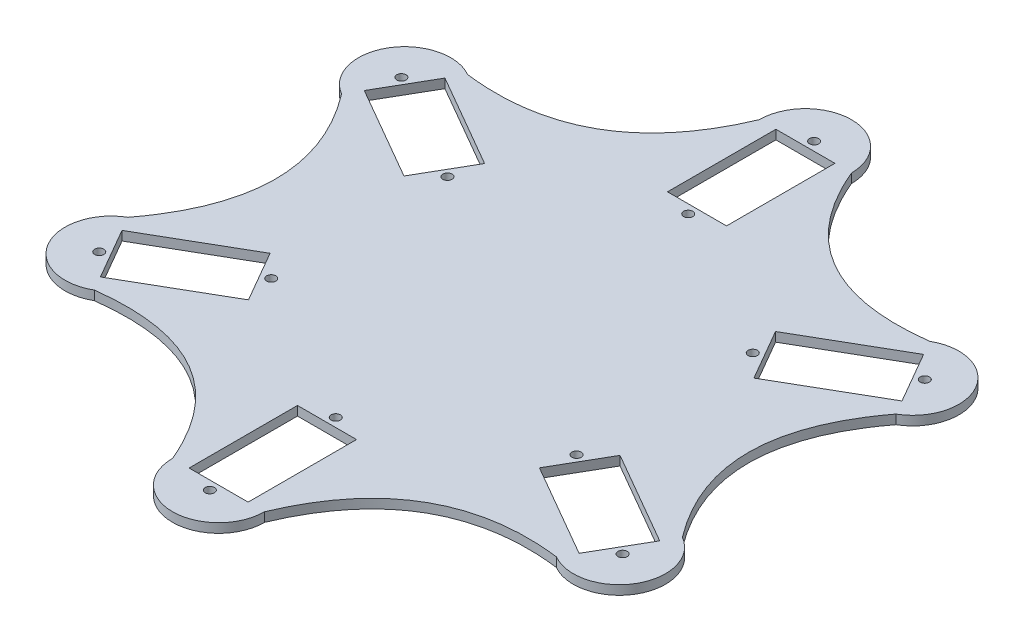
SolidWorks part; units mm, degrees
ref_plane "Front Plane" through (0, 0, 0) normal (0, 0, 1) x (1, 0, 0)
ref_plane "Top Plane" through (0, 0, 0) normal (0, 1, 0) x (1, 0, 0)
ref_plane "Right Plane" through (0, 0, 0) normal (1, 0, 0) x (0, 0, -1)
sketch "Sketch4" plane through (0, 0, 0) normal (0, 1, 0) x (1, 0, 0)
  line L0 (0, 0) -> (0, 73.6122) construction
  line L2 (42.5, 73.6122) -> (-42.5, 73.6122)
  line L5 (-6.4, 40.1122) -> (6.4, 40.1122)
  line L6 (-6.4, 40.1122) -> (-6.4, 63.6122)
  line L7 (-6.4, 63.6122) -> (6.4, 63.6122)
  line L8 (6.4, 40.1122) -> (6.4, 63.6122)
  line L9 (-6.4, 40.1122) -> (6.4, 63.6122) construction
  line L10 (-6.4, 63.6122) -> (6.4, 40.1122) construction
  line L11 (85, 0) -> (42.5, 73.6122)
  line L12 (42.5, 73.6122) -> (0, 0) construction
  line L13 (31.5381, 25.5986) -> (37.9381, 14.5135)
  line L14 (31.5381, 25.5986) -> (51.8897, 37.3486)
  line L15 (51.8897, 37.3486) -> (58.2897, 26.2635)
  line L16 (37.9381, 14.5135) -> (58.2897, 26.2635)
  line L17 (0, 0) -> (63.75, 36.8061) construction
  line L18 (31.5381, 25.5986) -> (58.2897, 26.2635) construction
  line L19 (51.8897, 37.3486) -> (37.9381, 14.5135) construction
  line L21 (42.5, -73.6122) -> (85, 0)
  line L22 (85, 0) -> (0, 0) construction
  line L23 (37.9381, -14.5135) -> (31.5381, -25.5986)
  line L24 (37.9381, -14.5135) -> (58.2897, -26.2635)
  line L25 (58.2897, -26.2635) -> (51.8897, -37.3486)
  line L26 (31.5381, -25.5986) -> (51.8897, -37.3486)
  line L27 (0, 0) -> (63.75, -36.8061) construction
  line L28 (37.9381, -14.5135) -> (51.8897, -37.3486) construction
  line L29 (58.2897, -26.2635) -> (31.5381, -25.5986) construction
  line L30 (0, 0) -> (-42.5, -73.6122) construction
  line L31 (-42.5, -73.6122) -> (42.5, -73.6122)
  line L32 (42.5, -73.6122) -> (0, 0) construction
  line L33 (6.4, -40.1122) -> (-6.4, -40.1122)
  line L34 (6.4, -40.1122) -> (6.4, -63.6122)
  line L35 (6.4, -63.6122) -> (-6.4, -63.6122)
  line L36 (-6.4, -40.1122) -> (-6.4, -63.6122)
  line L37 (0, 0) -> (0, -73.6122) construction
  line L38 (6.4, -40.1122) -> (-6.4, -63.6122) construction
  line L39 (6.4, -63.6122) -> (-6.4, -40.1122) construction
  line L40 (0, 0) -> (-85, 0) construction
  line L41 (-85, 0) -> (-42.5, -73.6122)
  line L43 (-31.5381, -25.5986) -> (-37.9381, -14.5135)
  line L44 (-31.5381, -25.5986) -> (-51.8897, -37.3486)
  line L45 (-51.8897, -37.3486) -> (-58.2897, -26.2635)
  line L46 (-37.9381, -14.5135) -> (-58.2897, -26.2635)
  line L47 (0, 0) -> (-63.75, -36.8061) construction
  line L48 (-31.5381, -25.5986) -> (-58.2897, -26.2635) construction
  line L49 (-51.8897, -37.3486) -> (-37.9381, -14.5135) construction
  line L50 (0, 0) -> (-42.5, 73.6122) construction
  line L51 (-42.5, 73.6122) -> (-85, 0)
  line L53 (-37.9381, 14.5135) -> (-31.5381, 25.5986)
  line L54 (-37.9381, 14.5135) -> (-58.2897, 26.2635)
  line L55 (-58.2897, 26.2635) -> (-51.8897, 37.3486)
  line L56 (-31.5381, 25.5986) -> (-51.8897, 37.3486)
  line L57 (0, 0) -> (-63.75, 36.8061) construction
  line L58 (-37.9381, 14.5135) -> (-51.8897, 37.3486) construction
  line L59 (-58.2897, 26.2635) -> (-31.5381, 25.5986) construction
  line L60 (-6.4, 63.6122) -> (6.4, 63.6122)
  line L61 (-6.4, 63.6122) -> (-6.4, 68.3122) construction
  line L62 (6.4, 63.6122) -> (6.4, 68.3122) construction
  line L63 (-6.4, 68.3122) -> (6.4, 68.3122) construction
  line L64 (-55.0574, 51.8622) -> (55.0574, 51.8622) construction
  line L65 (-10, 63.6122) -> (10, 63.6122) construction
  line L66 (50.0897, 40.4663) -> (60.0897, 23.1458) construction
  line L67 (60.0897, -23.1458) -> (50.0897, -40.4663) construction
  line L68 (10, -63.6122) -> (-10, -63.6122) construction
  line L69 (-50.0897, -40.4663) -> (-60.0897, -23.1458) construction
  line L70 (-60.0897, 23.1458) -> (-50.0897, 40.4663) construction
  line L71 (-10, 63.6122) -> (-21.25, 36.8061) construction
  line L72 (-21.25, 36.8061) -> (-50.0897, 40.4663) construction
  line L73 (50.0897, 40.4663) -> (21.25, 36.8061) construction
  line L74 (21.25, 36.8061) -> (10, 63.6122) construction
  line L75 (60.0897, -23.1458) -> (42.5, 0) construction
  line L76 (42.5, 0) -> (60.0897, 23.1458) construction
  line L77 (10, -63.6122) -> (21.25, -36.8061) construction
  line L78 (21.25, -36.8061) -> (50.0897, -40.4663) construction
  line L79 (-50.0897, -40.4663) -> (-21.25, -36.8061) construction
  line L80 (-21.25, -36.8061) -> (-10, -63.6122) construction
  line L81 (-60.0897, 23.1458) -> (-42.5, 0) construction
  line L82 (-42.5, 0) -> (-60.0897, -23.1458) construction
  circle A0 centre (0, 65.5122) radius 1
  circle A1 centre (56.7352, 32.7561) radius 1
  circle A2 centre (56.7352, -32.7561) radius 1
  circle A3 centre (0, -65.5122) radius 1
  circle A4 centre (-56.7352, -32.7561) radius 1
  circle A5 centre (-56.7352, 32.7561) radius 1
  circle A6 centre (0, 38.2122) radius 1
  circle A7 centre (33.0927, 19.1061) radius 1
  circle A8 centre (33.0927, -19.1061) radius 1
  circle A9 centre (0, -38.2122) radius 1
  circle A10 centre (-33.0927, -19.1061) radius 1
  circle A11 centre (-33.0927, 19.1061) radius 1
  circle A12 centre (0, 0) radius 73.6122
  circle A14 centre (0, 63.6122) radius 10
  circle A15 centre (55.0897, 31.8061) radius 10
  circle A16 centre (55.0897, -31.8061) radius 10
  circle A17 centre (0, -63.6122) radius 10
  circle A18 centre (-55.0897, -31.8061) radius 10
  circle A19 centre (-55.0897, 31.8061) radius 10
  spline S0 degree 2 poles (-10, 63.6122) (-21.25, 36.8061) (-50.0897, 40.4663) knots 0 0 0 1 1 1
  spline S1 degree 2 poles (50.0897, 40.4663) (21.25, 36.8061) (10, 63.6122) knots 0 0 0 1 1 1
  spline S2 degree 2 poles (60.0897, -23.1458) (42.5, 0) (60.0897, 23.1458) knots 0 0 0 1 1 1
  spline S3 degree 2 poles (10, -63.6122) (21.25, -36.8061) (50.0897, -40.4663) knots 0 0 0 1 1 1
  spline S4 degree 2 poles (-50.0897, -40.4663) (-21.25, -36.8061) (-10, -63.6122) knots 0 0 0 1 1 1
  spline S5 degree 2 poles (-60.0897, 23.1458) (-42.5, 0) (-60.0897, -23.1458) knots 0 0 0 1 1 1
  point P0 (0, 73.6122)
  point P6 (0, 51.8622)
  point P14 (63.75, 36.8061)
  point P16 (0, 0)
  point P18 (44.9139, 25.9311)
  point P23 (63.75, -36.8061)
  point P27 (44.9139, -25.9311)
  point P32 (0, -73.6122)
  point P36 (0, -51.8622)
  point P41 (-63.75, -36.8061)
  point P45 (-44.9139, -25.9311)
  point P50 (-63.75, 36.8061)
  point P52 (-56.7352, 32.7561)
  point P54 (-44.9139, 25.9311)
  point P59 (0, 0)
  point P63 (0, 0)
  point P76 (0, 0)
  point P77 (0, 51.8622)
  point P92 (0, 0)
  point P113 (0, 0)
  point P118 (-21.25, 36.8061)
  point P132 (0, 0)
  dimension "D9" = 2
  dimension "D2" = 6
  dimension "D12" = 6
  dimension "D1" = 85
  dimension "D3" = 23.5
  dimension "D4" = 12.8
  dimension "D5" = 10
  dimension "D7" = 4.7
  dimension "D8" = 27.3
  dimension "D6" = 6
  dimension "D10" = 6
  dimension "D11" = 6
extrude "Boss-Extrude3" add sketch "Sketch4" along normal blind 2 contours A12 A10 A8 A6 A5 A4 A3 A2 A1 A0 L56 L53 L54 L55 L8 L5 L6 L7 L16 L13 L14 L15 L26 L23 L24 L25 L36 L33 L34 L35 L46 | L8 A14 L6 L7 A0 | A15 L14 L15 L16 A1 | A16 L24 L25 L26 A2 | A17 L34 L35 L36 A3 | L46 A18 L44 L45 A4 | L56 A19 L54 L55 A5 region at (6.8823, 0, -70.4945) region at (64.4768, 0, -34.3213) region at (-57.605, 0, -41.1931) region at (0, 0, 0) region at (-64.4768, 0, 29.2908) region at (57.605, 0, 41.1931) region at (-6.8823, 0, 70.4945)
